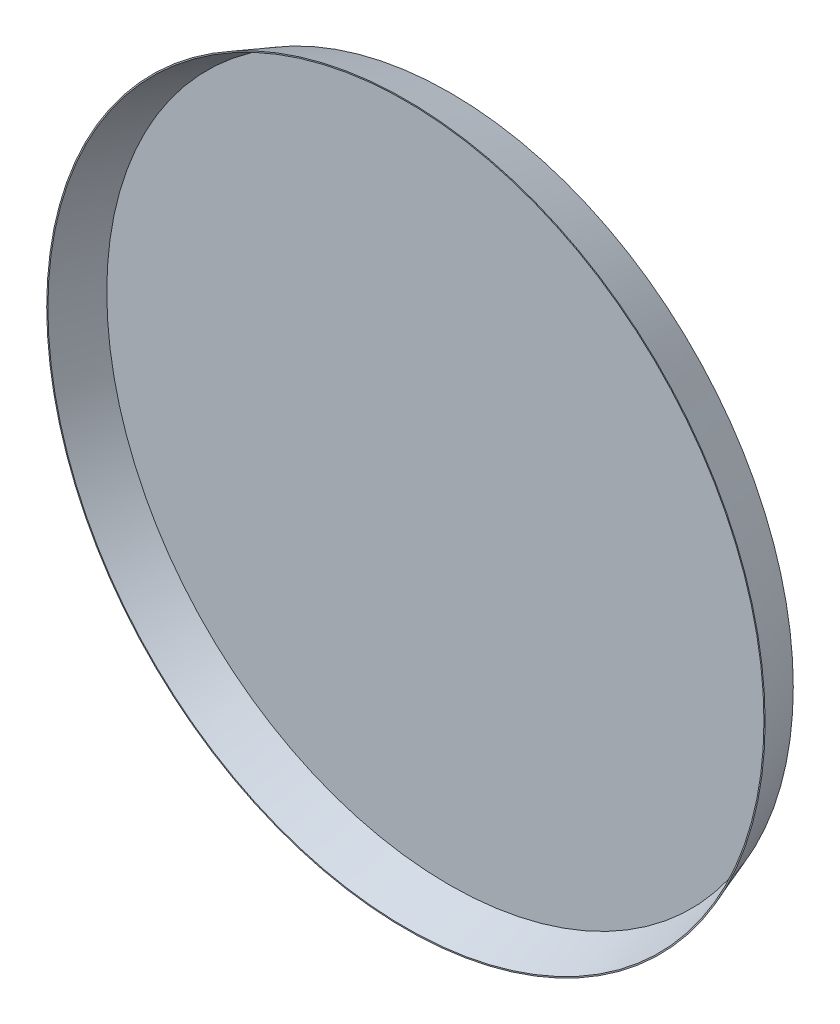
SolidWorks part; units mm, degrees
ref_plane "Front" through (0, 0, 0) normal (0, 0, 1) x (1, 0, 0)
ref_plane "Top" through (0, 0, 0) normal (0, 1, 0) x (1, 0, 0)
ref_plane "Right" through (0, 0, 0) normal (1, 0, 0) x (0, 0, -1)
sketch "Sketch1" plane through (0, 0, 0) normal (0, 0, 1) x (1, 0, 0)
  circle A0 centre (0, 0) radius 15.5
  dimension "D1" = 31
extrude "Base-Extrude" add sketch "Sketch1" along normal blind 2 draft 20 draft outward yes
shell "Shell1" thickness 0.05 removed face at (16.2279, 0, 2)
sketch "Sketch2" plane through (0, 0, 0.05) normal (0, 0, 1) x (1, 0, 0)
  line L0 (-19.075, 0) -> (20.9062, 0) construction
  line L1 (0, 17.0302) -> (0, -17.1523) construction
  circle A0 centre (10, 0) radius 1.75
  circle A1 centre (-7.5, 0) radius 4.05
  circle A2 centre (0, 7.5) radius 4.05
  circle A3 centre (0, -7.5) radius 4.05
  circle A4 centre (0, 0) radius 0.5
  dimension "D1" = 8.1
  dimension "D2" = 8.1
  dimension "D3" = 8.1
  dimension "D4" = 3.5
  dimension "D5" = 10
  dimension "D6" = 7.5
  dimension "D7" = 7.5
  dimension "D8" = 7.5
  dimension "D9" = 1
extrude "Cut-Extrude1" [suppressed] cut sketch "Sketch2" against normal through all
sketch "Sketch4" plane through (0, 0, 0.05) normal (0, 0, 1) x (1, 0, 0)
  line L0 (0, 0) -> (20, 0) construction
  line L1 (0, 0) -> (17.3205, -10) construction
  line L2 (0, 0) -> (10, -17.3205) construction
  line L3 (0, 0) -> (0, -20) construction
  line L4 (0, 0) -> (-10, -17.3205) construction
  line L5 (0, 0) -> (-17.3205, -10) construction
  line L6 (0, 0) -> (-20, 0) construction
  line L7 (0, 0) -> (-17.3205, 10) construction
  line L8 (0, 0) -> (-10, 17.3205) construction
  line L9 (0, 0) -> (0, 20) construction
  line L10 (0, 0) -> (10, 17.3205) construction
  line L11 (0, 0) -> (17.3205, 10) construction
  circle A0 centre (0, 0) radius 10
  dimension "D1" = 20
  dimension "D2" = 20
sketch "Sketch5" [suppressed] plane through (0, 0, 0.05) normal (0, 0, 1) x (1, 0, 0)
  circle A0 centre (-7.5, 0) radius 0.095
  circle A1 centre (0, -7.5) radius 0.095
  circle A2 centre (0, 7.5) radius 0.095
extrude "Cut-Extrude2" [suppressed] cut sketch "Sketch5" against normal through all
